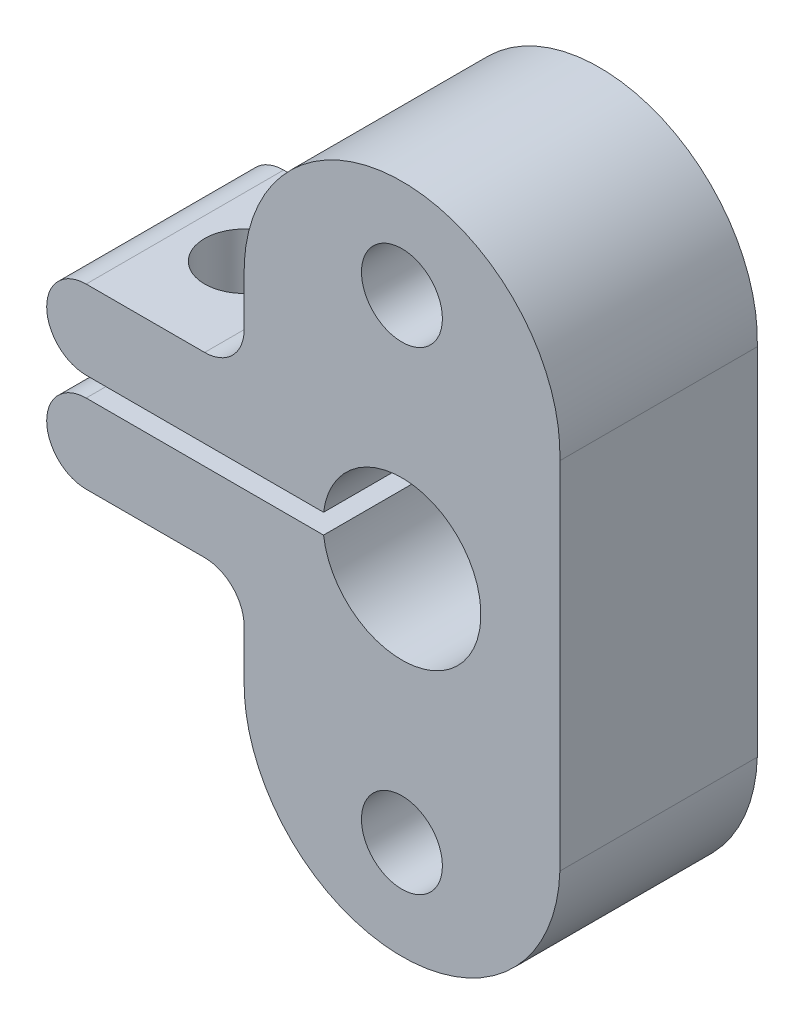
SolidWorks part; units mm, degrees
ref_plane "Plano frontal" through (0, 0, 0) normal (0, 0, 1) x (1, 0, 0)
ref_plane "Plano superior" through (0, 0, 0) normal (0, 1, 0) x (1, 0, 0)
ref_plane "Plano direito" through (0, 0, 0) normal (1, 0, 0) x (0, 0, -1)
sketch "Esboço1" plane through (0, 0, 0) normal (0, 0, 1) x (1, 0, 0)
  line L0 (0.004, -9.0015) -> (0.004, 9.0015) construction
  line L1 (-7.992, -8.75) -> (-7.992, -4.5)
  line L2 (8, -9.253) -> (8, 8.747)
  line L3 (0, 0) -> (-20, 0) construction
  line L4 (-8, -0.5) -> (-17.992, -0.5)
  line L5 (-17.992, -0.5) -> (-17.992, -4.5)
  line L6 (-17.992, -4.5) -> (-7.992, -4.5)
  line L7 (-8, -0.5) -> (-3.9686, -0.5)
  line L8 (-8, 0.5) -> (-3.9686, 0.5)
  line L9 (-8, 0.5) -> (-17.992, 0.5)
  line L10 (-17.992, 0.5) -> (-17.992, 4.5)
  line L11 (-17.992, 4.5) -> (-7.992, 4.5)
  line L12 (-7.992, 4.5) -> (-7.992, 8.75)
  arc A0 (-3.9686, -0.5) -> (-3.9686, 0.5) centre (0, 0) ccw
  arc A1 (-7.992, -8.75) -> (8, -9.253) centre (0.004, -9.0015) ccw
  arc A2 (8, 8.747) -> (-7.992, 8.75) centre (0.004, 9.0015) ccw
  circle A3 centre (0, 12) radius 2.05
  circle A4 centre (0, -12) radius 2.05
  point P1 (0.0055, 17.0015)
  point P5 (0, 0)
  point P25 (-0.2475, -16.9976)
  dimension "D1" = 8
  dimension "D3" = 8
  dimension "D4" = 4.1
  dimension "D5" = 12
  dimension "D6" = 12
  dimension "D14" = 8
  dimension "D2" = 18
  dimension "D7" = 20
  dimension "D8" = 4
  dimension "D9" = 0.5
  dimension "D10" = 10
  dimension "D11" = 34
  dimension "D12" = 16
  dimension "D13" = 4.25
extrude "Ressalto-extrusão1" add sketch "Esboço1" along normal blind 10
sketch "Esboço2" plane through (0, -4.5, 0) normal (0, -1, 0) x (1, 0, 0)
  line L0 (-17.992, 10) -> (-17.992, 0) construction
  line L1 (-7.992, 0) -> (-17.992, 0) construction
  circle A0 centre (-12.992, 5) radius 2
  dimension "D1" = 4
  dimension "D2" = 5
  dimension "D3" = 5
extrude "Corte-extrusão1" cut sketch "Esboço2" against normal up to surface (9 mm away) up to face at (-12.992, 4.5, 5)
fillet "Filete1" radius 2 6 edges at (-7.992, -4.5, 5) (-7.992, 4.5, 5) (-17.992, -4.5, 5) (-17.992, 0.5, 5) (-17.992, -0.5, 5) (-17.992, 4.5, 5)
